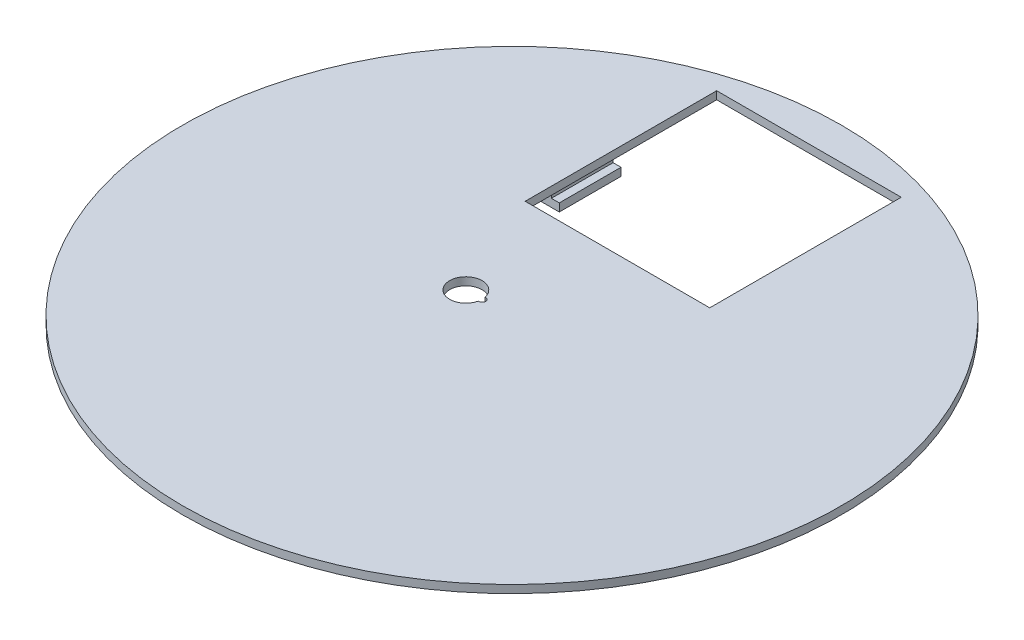
SolidWorks part; units mm, degrees
note: The reader was unsure of these and kept them because the rebuilt part matched: shared geometry of "Çizim6<3>", "Çizim8<4>".
ref_plane "Ön Düzlem" through (0, 0, 0) normal (0, 0, 1) x (1, 0, 0)
ref_plane "Üst Düzlem" through (0, 0, 0) normal (0, 1, 0) x (1, 0, 0)
ref_plane "Sağ Düzlem" through (0, 0, 0) normal (1, 0, 0) x (0, 0, -1)
sketch "Çizim1" plane through (0, 0, 0) normal (0, 1, 0) x (1, 0, 0)
  line L1 (-35, 112.6356) -> (35, 112.6356)
  line L2 (-35, 112.6356) -> (-35, 40)
  line L3 (-35, 40) -> (35, 40)
  line L4 (35, 112.6356) -> (35, 40)
  circle A0 centre (0, 0) radius 125
  point P9 (0, 0)
  point P10 (0, 40)
  dimension "D1" = 250
  dimension "D2" = 70
  dimension "D3" = 40
extrude "Yükseklik-Ekstrüzyon1" add sketch "Çizim1" along normal blind 3
sketch "Çizim6" plane through (0, 0, 0) normal (0, -1, 0) x (1, 0, 0)
  line L0 (-35, -112.6356) -> (-35, -40) construction
  line L1 (-35, -52.9352) -> (-42, -52.9352)
  line L2 (-35, -52.9352) -> (-35, -76.3504)
  line L3 (-35, -76.3504) -> (-42, -76.3504)
  line L4 (-42, -52.9352) -> (-42, -76.3504)
  line L5 (-38, -52.9352) -> (-38, -76.3504)
  dimension "D1" = 7
  dimension "D2" = 3
extrude "Yükseklik-Ekstrüzyon3" add sketch "Çizim6" along normal blind 4 contours L5 L1 L4 L3
extrude "Yükseklik-Ekstrüzyon4" add sketch "Çizim6<3>" along normal blind 3 from surface at 4 contours L1 L4 L3 L2 starting at face at (-40, -4, -64.6428)
sketch "Çizim6<3>" plane through (0, 0, 0) normal (0, -1, 0) x (1, 0, 0) same geometry as "Çizim6"
sketch "Çizim8" plane through (0, 0, 0) normal (0, -1, 0) x (1, 0, 0)
  line L4 (-37.9018, -77.2074) -> (34.8544, -77.2074)
  line L5 (34.8544, -77.2074) -> (34.8544, 41.7395)
  line L6 (34.8544, 41.7395) -> (-37.9018, 41.7395)
  line L7 (-37.9018, 41.7395) -> (-37.9018, -77.2074)
  line L8 (-37.9018, -77.2074) -> (34.8544, -77.2074)
  line L9 (34.8544, -77.2074) -> (34.8544, 41.7395)
  line L10 (34.8544, 41.7395) -> (-37.9018, 41.7395)
  line L11 (-37.9018, 41.7395) -> (-37.9018, -77.2074)
  circle A1 centre (4.3186, -2.1026) radius 2.5
  circle A3 centre (4.3186, -2.1026) radius 4.5
  circle A9 centre (2.948, 26.2556) radius 2.2552
  circle A10 centre (2.948, 26.2556) radius 2.2552
  arc A12 (-29.7668, 26.2556) -> (2.948, -6.4592) centre (2.948, 26.2556) ccw
  arc A13 (-22.7668, 26.2556) -> (-29.7668, 26.2556) centre (-26.2668, 26.2556) ccw
  arc A14 (-22.7668, 26.2556) -> (2.948, 0.5408) centre (2.948, 26.2556) ccw
  arc A15 (2.948, -6.4592) -> (2.948, 0.5408) centre (2.948, -2.9592) ccw
  arc A16 (3.1883, -6.4583) -> (5.8637, -6.329) centre (2.948, 26.2556) ccw
  arc A18 (0.7472, 0.6351) -> (2.948, 0.5408) centre (2.948, 26.2556) ccw
  dimension "D1" = 5
  dimension "D3" = 0
  dimension "D2" = 2
  dimension "D4" = 0
  dimension "D5" = 0
extrude "Yükseklik-Ekstrüzyon5" add sketch "Çizim8" along normal up to vertex (3 mm away) contours A1
extrude "Yükseklik-Ekstrüzyon6" add sketch "Çizim8<4>" along normal blind 3 from vertex at 3
sketch "Çizim8<4>" plane through (0, 0, 0) normal (0, -1, 0) x (1, 0, 0) same geometry as "Çizim8"
sketch "Çizim10" plane through (0, 0, 0) normal (0, -1, 0) x (1, 0, 0)
  arc A0 (-11.0978, 1.6381) -> (-11.0978, -0.8704) centre (-17.1186, 0.3838) ccw
  arc A2 (-11.0978, -0.8704) -> (-11.0978, 1.6381) centre (-10.8686, 0.3838) ccw
extrude "Kes-Ekstrüzyon1" cut sketch "Çizim10" against normal through all
